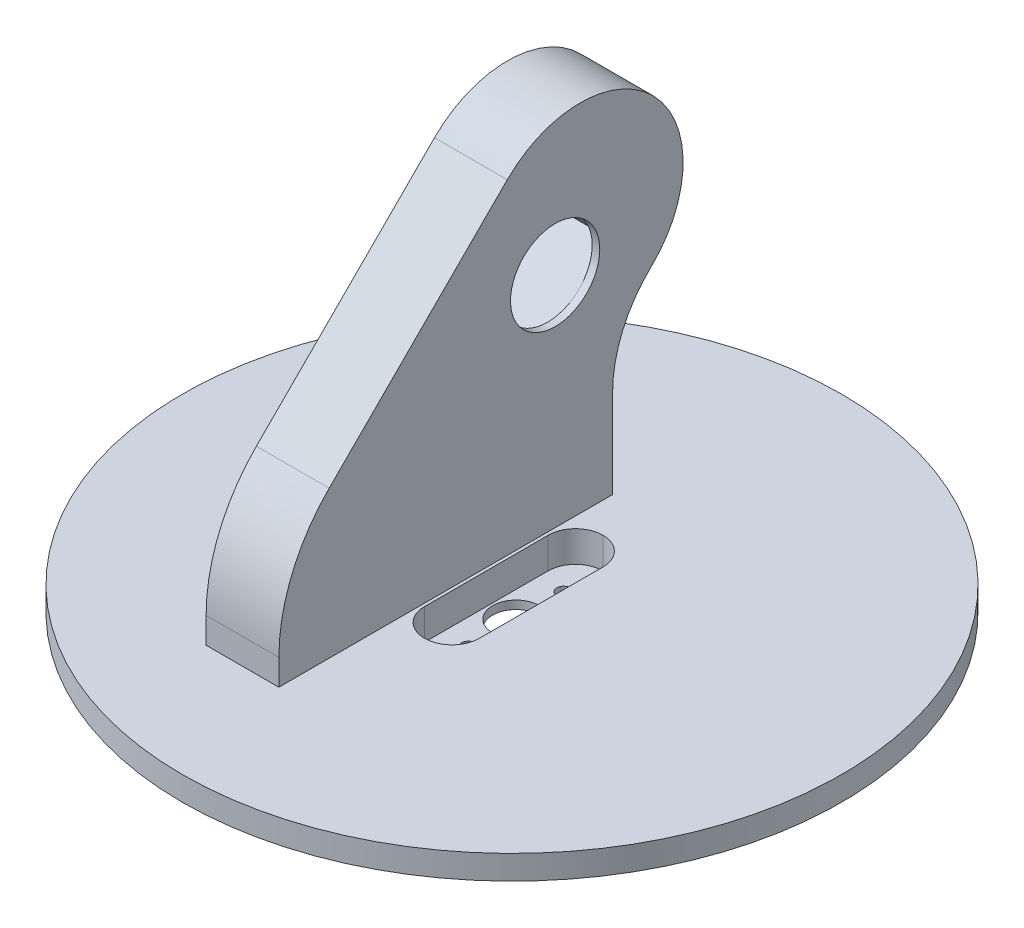
SolidWorks part; units mm, degrees
ref_plane "Front Plane" through (0, 0, 0) normal (0, 0, 1) x (1, 0, 0)
ref_plane "Top Plane" through (0, 0, 0) normal (0, 1, 0) x (1, 0, 0)
ref_plane "Right Plane" through (0, 0, 0) normal (1, 0, 0) x (0, 0, -1)
sketch "Sketch2" plane through (0, 0, 0) normal (0, 1, 0) x (1, 0, 0)
  circle A0 centre (0, 0) radius 48
  dimension "D1" = 96
extrude "Boss-Extrude1" add sketch "Sketch2" along normal blind 3.5
ref_plane "Plane1" through (-4, 0, 0) normal (1, 0, 0) x (0, 0, -1)
sketch "Sketch7" plane through (-4, 0, 0) normal (1, 0, 0) x (0, 0, -1)
  line L0 (18.6521, 16.3561) -> (18.6521, 3.5)
  line L5 (48, 3.5) -> (-48, 3.5) construction
  line L6 (-22.6311, 24.9401) -> (3.3119, 50.8831)
  line L7 (-43.5609, 3.5) -> (18.6521, 3.5)
  line L11 (-29.9535, 3.5) -> (-29.9535, 7.2624)
  arc A4 (24.252, 29.4036) -> (3.3119, 50.8831) centre (13.9185, 40.2765) ccw
  arc A5 (24.252, 29.4036) -> (18.6521, 16.3561) centre (36.6521, 16.3561) ccw
  arc A6 (-22.6311, 24.9401) -> (-29.9535, 7.2624) centre (-4.9535, 7.2624) ccw
  dimension "D1" = 25
  dimension "D4" = 30
  dimension "D3" = 18
  dimension "D5" = 45
extrude "Boss-Extrude2" add sketch "Sketch7" against normal blind 10.6 contours A5 A4 L6 L7 L0 | A4 | A4 | A4 | L6 A6 L7 region at (-4, 25.827, -1.7732)
ref_plane "Plane2" through (-6, 0, 0) normal (1, 0, 0) x (0, 0, -1)
sketch "Sketch31" plane through (-14.6, 10.4618, -5.3595) normal (-1, 0, 0) x (0, 0, 1)
  line L0 (-5.4155, 34.0546) -> (11.7496, 18.7458)
  line L1 (11.7496, 18.7458) -> (3.0968, 9.0438)
  line L2 (3.0968, 9.0438) -> (-14.0683, 24.3526)
  line L3 (-14.0683, 24.3526) -> (-5.4155, 34.0546)
  circle A0 centre (-4.9225, 24.9054) radius 6.5
  dimension "D1" = 6.5
extrude "Cut-Extrude18" cut sketch "Sketch31" against normal through all contours A0
extrude "Cut-Extrude19" cut sketch "Sketch31<3>" against normal blind 9.5 contours L0 L1 L2 L3
sketch "Sketch31<3>" plane through (-14.6, 10.4618, -5.3595) normal (-1, 0, 0) x (0, 0, 1) same geometry as "Sketch31"
sketch "Sketch32" plane through (-14.6, 0, 0) normal (-1, 0, 0) x (0, 0, 1)
  line L0 (6.3901, 29.2076) -> (-2.2627, 19.5056) construction
  circle A0 centre (-17.0806, 41.2645) radius 1
  circle A1 centre (3.9294, 22.6926) radius 1
  arc A3 (-14.6084, 40.2182) -> (-15.5944, 39.1126) centre (-10.282, 35.3672) ccw construction
  dimension "D1" = 2.5
  dimension "D2" = 2.5
extrude "Cut-Extrude20" cut sketch "Sketch32" against normal blind 4.5
sketch "Sketch33" plane through (0, 0, 0) normal (0, -1, 0) x (1, 0, 0)
  circle A0 centre (0, 0) radius 42.5
  dimension "D1" = 85
extrude "Boss-Extrude3" add sketch "Sketch33" along normal blind 2.2
sketch "Sketch34" plane through (-3.5685, 3.5, 15.3455) normal (0, 1, 0) x (1, 0, 0)
  line L1 (0, 2.1692) -> (8, 2.1692)
  line L2 (0, 2.1692) -> (0, 28.1692)
  line L3 (0, 28.1692) -> (8, 28.1692)
  line L4 (8, 2.1692) -> (8, 28.1692)
  dimension "D1" = 26
  dimension "D2" = 8
extrude "Cut-Extrude21" cut sketch "Sketch34" against normal blind 4.5
sketch "Sketch35" plane through (64.9204, 3.5, -6.6124) normal (0, 1, 0) x (1, 0, 0)
  circle A0 centre (-64.7222, -6.2183) radius 3.43
  dimension "D1" = 6.86
extrude "Cut-Extrude22" cut sketch "Sketch35" against normal through all
fillet "Fillet1" radius 4 4 edges at (4.4315, 1.25, 13.1763) (-3.5685, 1.25, 13.1763) (4.4315, 1.25, -12.8237) (-3.5685, 1.25, -12.8237)
sketch "Sketch38" plane through (0, -1, 0) normal (0, 1, 0) x (1, 0, 0)
  circle A0 centre (0.1982, 7.3241) radius 1
  circle A1 centre (0.1982, -6.5359) radius 1
  circle A3 centre (0.1982, 0.3941) radius 3.43 construction
  dimension "D1" = 3.5
  dimension "D2" = 3.5
extrude "Cut-Extrude25" cut sketch "Sketch38" against normal blind 4.5
